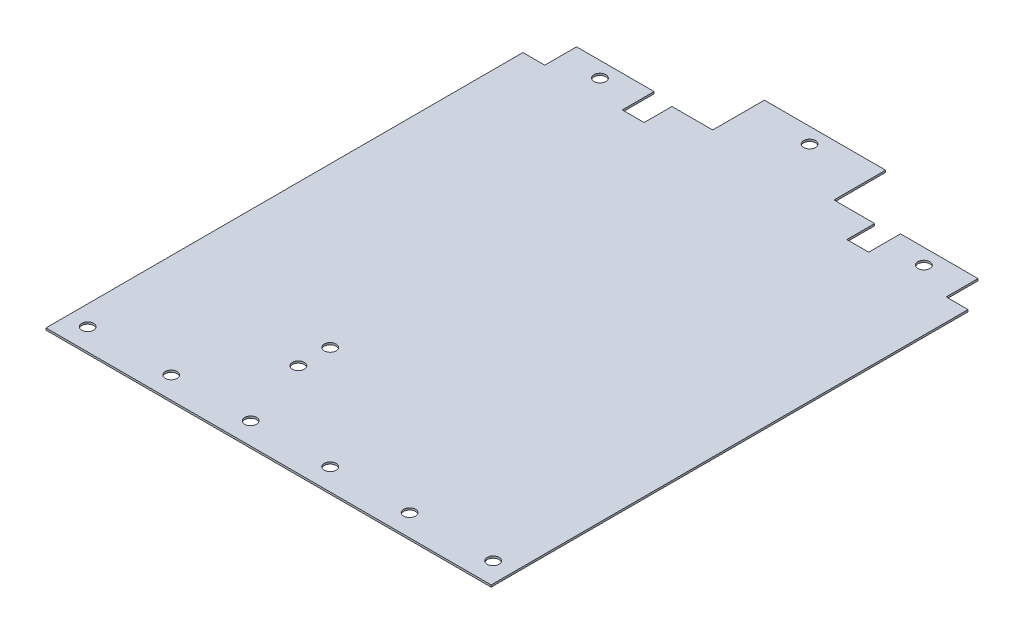
SolidWorks part; units mm, degrees
ref_plane "Front Plane" through (0, 0, 0) normal (0, 0, 1) x (1, 0, 0)
ref_plane "Top Plane" through (0, 0, 0) normal (0, 1, 0) x (1, 0, 0)
ref_plane "Right Plane" through (0, 0, 0) normal (1, 0, 0) x (0, 0, -1)
sketch "Croquis1" plane through (0, 0, 0) normal (0, 1, 0) x (1, 0, 0)
  line L1 (56, 70) -> (-56, 70)
  line L2 (56, 70) -> (56, -70)
  line L3 (56, -70) -> (-56, -70)
  line L4 (-56, 70) -> (-56, -70)
  line L5 (56, 70) -> (-56, -70) construction
  line L6 (56, -70) -> (-56, 70) construction
  point P0 (0, 0)
  dimension "D1" = 140
  dimension "D2" = 112
sheet metal parameters "Chapa metálica1" thickness 0.5 parameters "D1"=0.5, "Espesor"=0.5
base flange "Brida base1" sketch "Croquis1" thickness 0.5 reverse thickness direction no parameters "D1"=0.5
sketch "Croquis5" plane through (0, 0, 0) normal (0, 1, 0) x (1, 0, 0)
  line L0 (0, 98.1021) -> (0, -84.209) construction
  line L1 (0, 70.0129) -> (-15.25, 70)
  line L2 (56, 70) -> (-56, 70) construction
  line L3 (-15.25, 70) -> (-15.25, 57)
  line L4 (-15.25, 57) -> (-25.5, 57)
  line L5 (-25.5, 57) -> (-25.5, 50)
  line L6 (-25.5, 50) -> (-31, 50)
  line L7 (-56, 70) -> (-56, -70) construction
  line L8 (0, 70.0129) -> (15.25, 70)
  line L9 (15.25, 70) -> (15.25, 57)
  line L10 (15.25, 57) -> (25.5, 57)
  line L11 (25.5, 57) -> (25.5, 50)
  line L12 (25.5, 50) -> (31, 50)
  line L13 (-56, 50) -> (-56, 70)
  line L14 (-56, 70) -> (-15.25, 70)
  line L15 (15.25, 70) -> (56, 70)
  line L16 (56, 70) -> (56, 50)
  line L17 (-40.75, 80.7615) -> (-40.75, -9.086) construction
  line L18 (-50.5, 58) -> (-31, 58)
  line L19 (-50.5, 58) -> (-50.5, 50)
  line L20 (-31, 58) -> (-31, 50)
  line L21 (50.5, 58) -> (50.5, 50)
  line L22 (31, 58) -> (31, 50)
  line L23 (50.5, 58) -> (31, 58)
  line L24 (-50.5, 50) -> (-56, 50)
  line L25 (50.5, 50) -> (56, 50)
  point P29 (-40.75, 58)
  line M1 (-56, 70) -> (-56, -70)
  line M3 (56, -70) -> (56, 70)
  line M4 (56, 70) -> (-56, 70)
  dimension "D1" = 30.5
  dimension "D2" = 30.5
  dimension "D3" = 7
  dimension "D4" = 13
  dimension "D5" = 19.5
  dimension "D6" = 8
extrude "Cortar-Extruir1" cut sketch "Croquis5" against normal blind 10 contours L6 L5 L4 L3 M4 M1 | L11 L12 L9 L10 M3 M4 region at (36.1268, 0, -62.388) region at (-36.1268, 0, -62.388) normal cut yes
sketch "Croquis6" plane through (0, 0, 0) normal (0, 1, 0) x (1, 0, 0)
  line L0 (0, 95.7521) -> (0, -79.2859) construction
  line L1 (-40.75, 93.7722) -> (-40.75, -66.0818) construction
  line L2 (15.25, 70) -> (-15.25, 70) construction
  line L4 (-50.5, 58) -> (-31, 58) construction
  circle A0 centre (-40.75, 54.125) radius 1.5
  circle A1 centre (0, 66.125) radius 1.5
  circle A2 centre (40.75, 54.125) radius 1.5
  dimension "D3" = 3
  dimension "D4" = 3
  dimension "D1" = 3.875
  dimension "D2" = 3.875
extrude "Cortar-Extruir2" cut sketch "Croquis6" against normal blind 10 normal cut yes
sketch "Croquis7" plane through (0, 0, 0) normal (0, 1, 0) x (1, 0, 0)
  line L0 (-76.5583, -55) -> (71.6264, -55) construction
  line L1 (78.4466, -30) -> (-80.2784, -30) construction
  line L2 (-24, -80.9503) -> (-24, -15.3686) construction
  line L3 (-56, -70) -> (56, -70) construction
  line L4 (56, -70) -> (56, 50) construction
  line L5 (-16, -10.7879) -> (-16, -85.9617) construction
  line L6 (-76.5583, -42.5) -> (75.5103, -42.5) construction
  line L7 (-72.9339, -64.5) -> (65.6845, -64.5) construction
  line L8 (0, 85.7557) -> (0, -80.9503) construction
  line L9 (-56, 50) -> (-56, -70) construction
  circle A0 centre (-16, -38.5) radius 1.5
  circle A1 centre (-16, -46.5) radius 1.5
  circle A2 centre (-10, -64.5) radius 1.5
  circle A3 centre (-30, -64.5) radius 1.5
  circle A4 centre (30, -64.5) radius 1.5
  circle A5 centre (10, -64.5) radius 1.5
  circle A6 centre (-51, -64.5) radius 1.5
  circle A7 centre (51, -64.5) radius 1.5
  dimension "D6" = 3
  dimension "D8" = 3
  dimension "D9" = 3
  dimension "D13" = 3
  dimension "D1" = 15
  dimension "D2" = 25
  dimension "D3" = 80
  dimension "D4" = 8
  dimension "D5" = 12.5
  dimension "D7" = 8
  dimension "D10" = 20
  dimension "D11" = 10
  dimension "D12" = 5.5
  dimension "D14" = 5
extrude "Cortar-Extruir3" cut sketch "Croquis7" against normal blind 10 normal cut yes
flat pattern "Chapa desplegada1" [suppressed]
sketch "Líneas de pliegue1" plane through (0, 0, 0) normal (0, 1, 0) x (-1, 0, 0)
sketch3d "Cuadro delimitador1" [suppressed]
  line L0 (0, 0, 0) -> (0, -140, 0) construction
  line L1 (112, 0, 0) -> (112, -140, 0) construction
  line L2 (0, 0, 0) -> (112, 0, 0) construction
  line L3 (0, -140, 0) -> (112, -140, 0) construction
